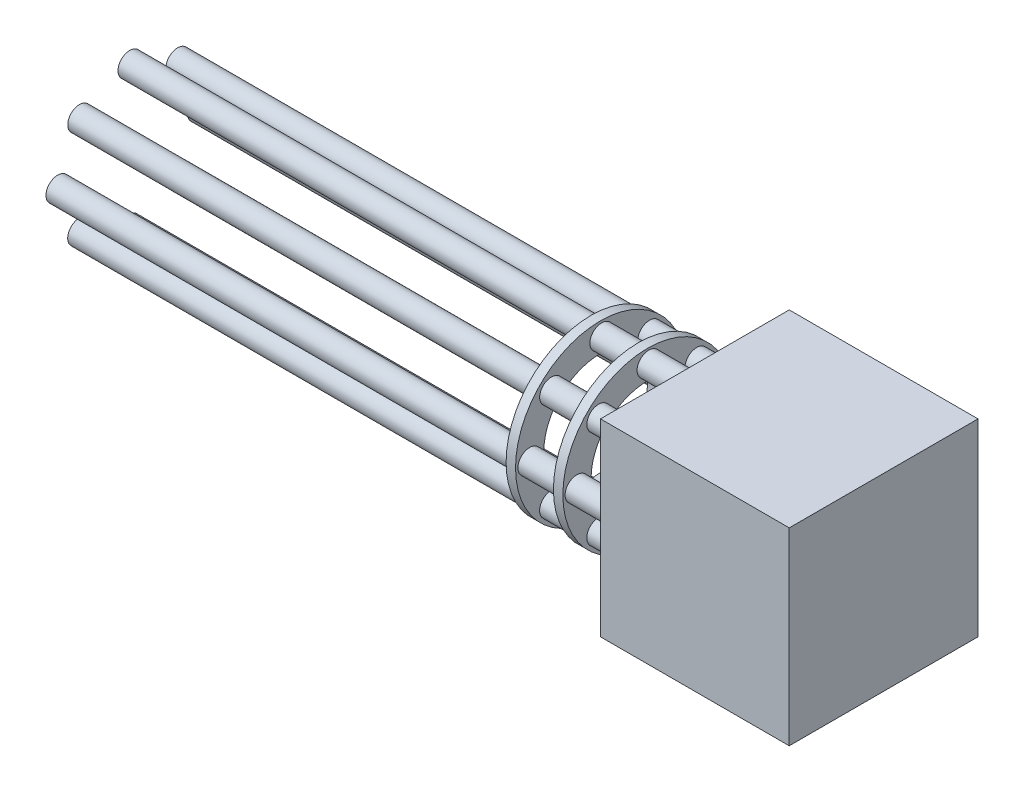
SolidWorks part; units mm, degrees
ref_plane "Front Plane" through (0, 0, 0) normal (0, 0, 1) x (1, 0, 0)
ref_plane "Top Plane" through (0, 0, 0) normal (0, 1, 0) x (1, 0, 0)
ref_plane "Right Plane" through (0, 0, 0) normal (1, 0, 0) x (0, 0, -1)
sketch "Sketch1" plane through (0, 0, 0) normal (0, 0, 1) x (1, 0, 0)
  line L0 (0, 0) -> (2000, 0)
  line L1 (2000, 0) -> (2000, 2000)
  line L2 (2000, 2000) -> (0, 2000)
  line L3 (0, 2000) -> (0, 0)
  dimension "D1" = 2000
  dimension "D2" = 2000
  dimension "D3" = 2000
extrude "Boss-Extrude1" add sketch "Sketch1" along normal blind 2000
sketch "Sketch2" plane through (0, 0, 0) normal (0, 0, 1) x (1, 0, 0)
  circle A0 centre (1000, 1000) radius 501.4041
ref_plane "Plane1" through (1000, 0, 0) normal (1, 0, 0) x (0, 0, -1)
sketch "Sketch4" plane through (1000, 0, 0) normal (1, 0, 0) x (0, 0, -1)
  line L0 (-1750, 1000) -> (-150, 1000)
  arc A0 (-150, 1000) -> (-1750, 1000) centre (-950, 1000) cw
revolve "Cut-Revolve1" cut sketch "Sketch4" angle 360 about L0
extrude "Cut-Extrude1" cut sketch "Sketch2" along normal blind 500 contours A0
sketch "Sketch5" plane through (1000, 0, 0) normal (1, 0, 0) x (0, 0, -1)
  point P6 (-1000, 1000)
ref_axis "Axis1" through (1000, 1000, 326.6269) along (0, 0, -1)
sketch "Sketch7" plane through (0, 0, 0) normal (1, 0, 0) x (0, 0, -1)
  line L1 (-2000, 0) -> (-2000, 2000) construction
  line L3 (-2000, 862.5528) -> (-1750, 862.5528)
  line L4 (-1750, 862.5528) -> (-1750, 1112.5528)
  line L5 (-1750, 1112.5528) -> (-2000, 1112.5528)
  line L6 (-2000, 862.5528) -> (-2000, 1112.5528)
  line L7 (0, 862.5528) -> (-250, 862.5528)
  line L8 (0, 2000) -> (0, 0) construction
  line L9 (-250, 862.5528) -> (-250, 1112.5528)
  line L10 (-250, 1112.5528) -> (0, 1112.5528)
  line L11 (0, 1112.5528) -> (0, 862.5528)
  line L12 (-875, 0) -> (-1125, 0)
  line L13 (-2000, 2000) -> (0, 2000) construction
  line L14 (-875, 0) -> (-875, 250)
  line L15 (-875, 250) -> (-1125, 250)
  line L16 (-1125, 250) -> (-1125, 0)
  line L17 (-862.9981, 2000) -> (-1112.1075, 2000)
  line L18 (-2000, 2000) -> (0, 2000) construction
  line L19 (-1112.1075, 2000) -> (-1112.1075, 1750)
  line L20 (-1112.1075, 1750) -> (-862.9981, 1750)
  line L21 (-862.9981, 1750) -> (-862.9981, 2000)
  line L22 (-1875, 1112.5528) -> (-1875, 862.5528)
  line L23 (-987.5528, 1750) -> (-987.5528, 2000)
  line L24 (-1000, 250) -> (-1000, 0)
  line L25 (-125, 1112.5528) -> (-125, 862.5528)
  line L26 (-1112.1075, 1750) -> (-1750, 1112.5528)
  line L27 (-862.9981, 1750) -> (-250, 1112.5528)
  line L28 (-250, 862.5528) -> (-875, 250)
  line L29 (-1125, 250) -> (-1750, 862.5528)
  line L31 (-2000, 0) -> (0, 0) construction
  line L32 (-2000, 2000) -> (-2000, 0) construction
  circle A1 centre (-987.5528, 1750) radius 124.5547
  circle A2 centre (-1750, 987.5528) radius 125
  circle A3 centre (-1000, 250) radius 125
  circle A4 centre (-250, 987.5528) radius 125
  circle A8 centre (-480, 1520) radius 125
  circle A9 centre (-1520, 1520) radius 124.427
  circle A10 centre (-1520, 480) radius 125
  circle A11 centre (-480, 480) radius 125
  circle A12 centre (-987.5528, 1018.6957) radius 298.2295
  circle A13 centre (-987.5528, 1018.6957) radius 731.3043
  point P47 (-1519.5574, 1540.8882)
  point P49 (0, 0)
  point P50 (-472.8044, 1540.8882)
  point P51 (-427.7449, 517.8638)
  point P52 (-1574.4952, 517.8638)
  point P55 (0, 0)
  point P56 (-407.6646, 513.9572)
  point P57 (-1566.546, 571.9597)
  point P58 (0, 0)
  point P59 (-1750, 970.1466)
  point P60 (-1520, 537.9966)
  point P61 (-472.8044, 537.9966)
  dimension "D9" = 480
  dimension "D2" = 250
  dimension "D3" = 250
  dimension "D4" = 250
  dimension "D5" = 250
  dimension "D6" = 250
  dimension "D7" = 875
  dimension "D8" = 480
  dimension "D10" = 480
  dimension "D11" = 480
  dimension "D12" = 480
  dimension "D13" = 1012.4472
  dimension "D14" = 480
  dimension "D15" = 480
  dimension "D16" = 480
extrude "Boss-Extrude4" add sketch "Sketch7" against normal blind 6000 contours A2 | A1 | A9 | A10 | A3 | A11 | A4 | A8
ref_plane "Plane4" through (-1000, 0, 0) normal (-1, 0, 0) x (0, 0, 1)
sketch "Sketch9" plane through (-1000, 0, 0) normal (-1, 0, 0) x (0, 0, 1)
  line L20 (543.6227, 372.4028) -> (1583.6227, 372.4028)
  circle A12 centre (480, 480) radius 125 construction
  circle A13 centre (1520, 480) radius 125 construction
  circle A14 centre (1000, 1000) radius 900
  circle A15 centre (1000, 1000) radius 600
ref_plane "Plane5" through (-500, 0, 0) normal (-1, 0, 0) x (0, 0, 1)
sketch "Sketch10" plane through (-500, 0, 0) normal (-1, 0, 0) x (0, 0, 1)
  circle A0 centre (1000, 1000) radius 476.6352
  circle A1 centre (1000, 1000) radius 898.5658
extrude "Boss-Extrude6" add sketch "Sketch9" along normal blind 100 contours A14
extrude "Boss-Extrude7" add sketch "Sketch10" along normal blind 100 contours A1
extrude "Cut-Extrude2" cut sketch "Sketch9<3>" against normal blind 600 and the other way blind 600 contours A15
sketch "Sketch9<3>" plane through (-1000, 0, 0) normal (-1, 0, 0) x (0, 0, 1) same geometry as "Sketch9"
sketch "Sketch11" plane through (-1000, 0, 0) normal (-1, 0, 0) x (0, 0, 1)
  circle A0 centre (480, 1520) radius 98.3511
  circle A1 centre (987.5528, 1750) radius 100.0313
  circle A2 centre (480, 480) radius 100.947
  circle A3 centre (1000, 250) radius 103.6368
  circle A4 centre (1520, 480) radius 97.3146
  circle A5 centre (1750, 987.5528) radius 98.6198
  circle A6 centre (1520, 1520) radius 100.3185
  circle A7 centre (250, 987.5528) radius 101.297
extrude "Cut-Extrude3" cut sketch "Sketch11" against normal blind 1000 and the other way through all
